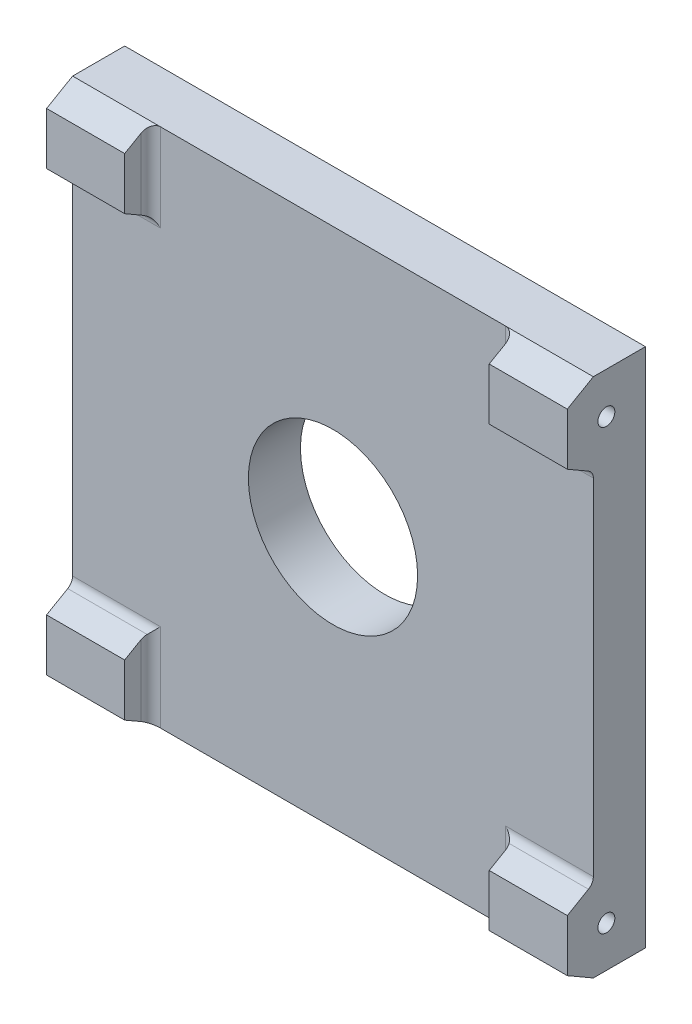
SolidWorks part; units mm, degrees
ref_plane "前视基准面" through (0, 0, 0) normal (0, 0, 1) x (1, 0, 0)
ref_plane "上视基准面" through (0, 0, 0) normal (0, 1, 0) x (1, 0, 0)
ref_plane "右视基准面" through (0, 0, 0) normal (1, 0, 0) x (0, 0, -1)
sketch "草图1" plane through (0, 0, 0) normal (0, 0, 1) x (1, 0, 0)
  line L1 (-40, 40) -> (40, 40)
  line L2 (-40, 40) -> (-40, -40)
  line L3 (-40, -40) -> (40, -40)
  line L4 (40, 40) -> (40, -40)
  line L5 (-40, 40) -> (40, -40) construction
  line L6 (-40, -40) -> (40, 40) construction
  point P0 (0, 0)
  dimension "D1" = 80
  dimension "D2" = 80
extrude "凸台-拉伸1" add sketch "草图1" along normal blind 8
sketch "草图6" plane through (0, 0, 8) normal (0, 0, 1) x (1, 0, 0)
  circle A0 centre (0, 0) radius 13
  dimension "D1" = 26
extrude "切除-拉伸3" cut sketch "草图6" against normal blind 50
sketch "草图7" plane through (-40, 0, 0) normal (-1, 0, 0) x (0, 0, 1)
  line L0 (0, 0) -> (8, 0) construction
  line L1 (0, 40) -> (0, -40) construction
  line L2 (8, 40) -> (8, -40) construction
  line L3 (8, 40) -> (8, 27.3812)
  line L4 (8, 27.3812) -> (12, 29.6906)
  line L5 (12, 29.6906) -> (12, 37.6906)
  line L6 (12, 37.6906) -> (8, 40)
  line L7 (12, -37.6906) -> (8, -40)
  line L8 (12, -29.6906) -> (12, -37.6906)
  line L9 (8, -27.3812) -> (12, -29.6906)
  line L10 (8, -40) -> (8, -27.3812)
  dimension "D1" = 4
  dimension "D2" = 60
  dimension "D3" = 60
  dimension "D4" = 8
extrude "凸台-拉伸2" add sketch "草图7" against normal blind 12
fillet "圆角1" radius 1.5 4 edges at (-34, 27.3812, 8) (-28, 33.6906, 8) (-28, -33.6906, 8) (-34, -27.3812, 8)
mirror "镜向1" about plane through (0, 0, 0) normal (1, 0, 0) of "圆角1", "凸台-拉伸2"
sketch "草图8" plane through (-40, 0, 0) normal (-1, 0, 0) x (0, 0, 1)
  line L0 (0, 40) -> (0, -40) construction
  circle A0 centre (6, 33.6906) radius 1.3
  circle A1 centre (6, -33.6906) radius 1.3
  dimension "D1" = 2.6
  dimension "D2" = 6
  dimension "D3" = 4
  dimension "D4" = 2.6
  dimension "D5" = 6
  dimension "D6" = 4
extrude "切除-拉伸4" cut sketch "草图8" against normal blind 10
mirror "镜向2" about plane through (0, 0, 0) normal (1, 0, 0) of "切除-拉伸4"
